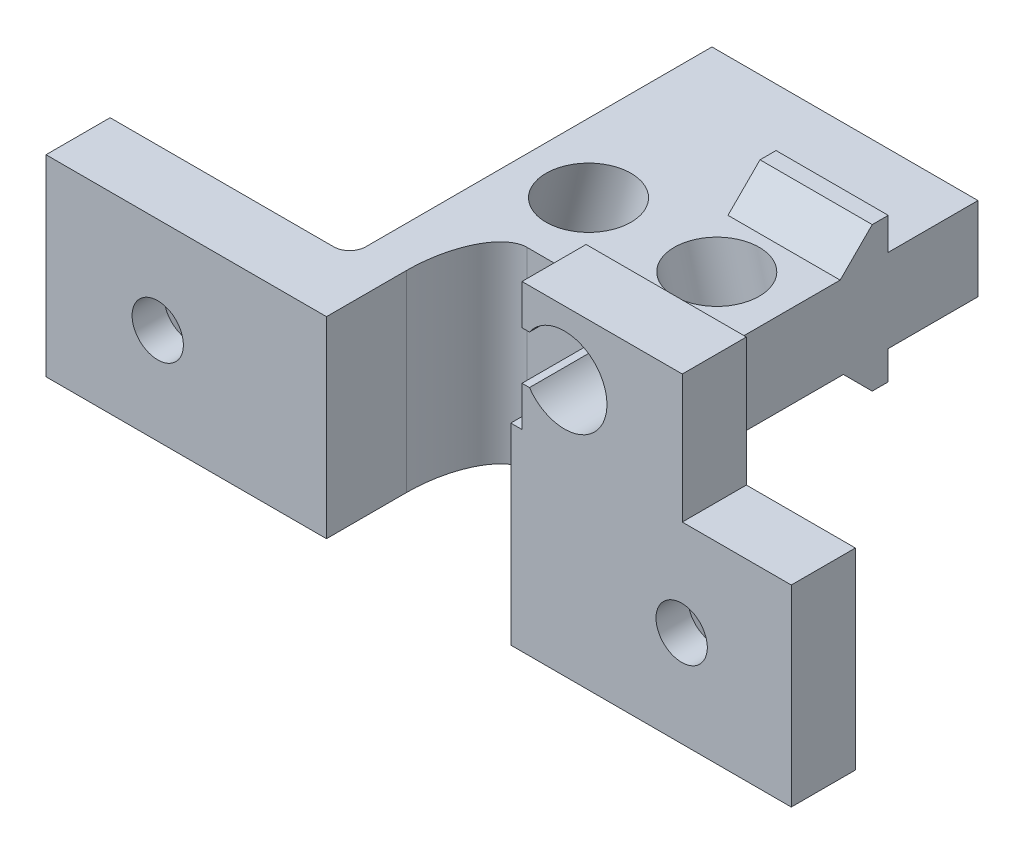
SolidWorks part; units mm, degrees
ref_plane "Front Plane" through (0, 0, 0) normal (0, 0, 1) x (1, 0, 0)
ref_plane "Top Plane" through (0, 0, 0) normal (0, 1, 0) x (1, 0, 0)
ref_plane "Right Plane" through (0, 0, 0) normal (1, 0, 0) x (0, 0, -1)
sketch "Sketch1" plane through (0, 0, 0) normal (0, 1, 0) x (1, 0, 0)
  line L0 (-3.25, -5) -> (-23.25, -5)
  line L1 (-3.25, -5) -> (3.25, -5) construction
  line L2 (-3.25, -5) -> (-3.25, 5) construction
  line L3 (-3.25, 5) -> (3.25, 5)
  line L4 (3.25, -5) -> (3.25, 5) construction
  line L5 (-3.25, -5) -> (3.25, 5) construction
  line L6 (-3.25, 5) -> (3.25, -5) construction
  line L7 (-23.25, -5) -> (-23.25, -1)
  line L8 (-23.25, -1) -> (-9.3, -1)
  line L9 (3.25, -5) -> (23.25, -5)
  line L10 (23.25, -5) -> (23.25, -3)
  line L12 (-8.3, 0) -> (-8.3, 6.6)
  line L13 (-8.3, 6.6) -> (8.3, 6.6)
  line L14 (8.3, 0) -> (8.3, 6.6)
  line L15 (-5.7498, 0) -> (-5.7498, -5)
  line L16 (5.7487, 0) -> (5.7487, -5)
  line L17 (23.25, -3) -> (23.25, -1)
  line L18 (23.25, -1) -> (9.3, -1)
  arc A0 (-9.3, -1) -> (-8.3, 0) centre (-9.3, 0) ccw
  arc A1 (9.3, -1) -> (8.3, 0) centre (9.3, 0) cw
  ellipse E0 centre (-3.25, 0) end of major axis (-3.25, 5) minor radius 2.4998 (-3.25, 5) -> (-3.25, -5) ccw
  ellipse E1 centre (3.25, 0) end of major axis (3.25, 5) minor radius 2.4987 (3.25, -5) -> (3.25, 5) ccw
  point P0 (0, 0)
  dimension "D6" = 1
  dimension "D7" = 4
  dimension "D12" = 1
  dimension "D1" = 6.5
  dimension "D2" = 10
  dimension "D3" = 20
  dimension "D4" = 4
  dimension "D5" = 20
  dimension "D8" = 16.6
  dimension "D9" = 1.6
  dimension "D10" = 5.05
  dimension "D11" = 5.05
extrude "Boss-Extrude1" add sketch "Sketch1" along normal blind 12 contours L8 L7 L0 E0 L3 E1 L9 L10 region at (-14.4999, 0, 4.5207)
sketch "Sketch2" plane through (0, 0, 1) normal (0, 0, -1) x (-1, 0, 0)
  line L0 (-23.3943, 12) -> (-9.4265, 0) construction
  line L1 (-23.25, 0) -> (-9.2822, 12) construction
  line L2 (23.25, 12) -> (9.3079, 0) construction
  line L3 (23.25, 0) -> (9.3, 0) construction
  line L4 (23.25, 0) -> (9.2822, 12) construction
  line L5 (-16.4104, 6) -> (-16.4104, -2.9743) construction
  line L6 (-16.4104, -0.7517) -> (-16.4104, 3) construction
  line L10 (16.2789, 6) -> (16.2789, -2.9743) construction
  line L11 (20.1472, 6) -> (18.2131, 9.35)
  line L12 (-12.5422, 6) -> (-14.4763, 9.35)
  line L13 (-14.4763, 9.35) -> (-18.3445, 9.35)
  line L14 (-18.3445, 9.35) -> (-20.2787, 6)
  line L15 (-20.2787, 6) -> (-18.3445, 2.65)
  line L16 (18.2131, 9.35) -> (14.3448, 9.35)
  line L17 (14.3448, 9.35) -> (12.4107, 6)
  line L18 (-18.3445, 2.65) -> (-14.4763, 2.65)
  line L19 (-14.4763, 2.65) -> (-12.5422, 6)
  line L20 (12.4107, 6) -> (14.3448, 2.65)
  line L21 (14.3448, 2.65) -> (18.2131, 2.65)
  line L22 (18.2131, 2.65) -> (20.1472, 6)
  circle A0 centre (-16.4104, 6) radius 3.35 construction
  circle A1 centre (16.2789, 6) radius 3.35 construction
  point P32 (11.4039, 0.6926)
  dimension "D1" = 6.7
  dimension "D2" = 6.7
extrude "Cut-Extrude1" cut sketch "Sketch2" against normal blind 2
sketch "Sketch3" plane through (0, 12, 0) normal (0, 1, 0) x (1, 0, 0)
  line L0 (-3.25, 5) -> (-3.25, 12.9854) construction
  line L1 (3.25, 5) -> (3.25, 12.9854) construction
  line L2 (-8.3, 6.6) -> (8.3, 6.6)
  line L3 (-8.1382, 9.4853) -> (3.25, 9.4853) construction
  line L4 (-10.9928, 20.2416) -> (10.7178, 20.2416) construction
  line L5 (-8.3, 6.6) -> (-8.3, 21.6)
  line L6 (-8.3, 21.6) -> (8.3, 21.6)
  line L7 (8.3, 21.6) -> (8.3, 6.6)
  circle A1 centre (3.25, 9.4853) radius 2.5 construction
  circle A3 centre (0, 0) radius 13.8 construction
  circle A4 centre (-3.25, 9.4853) radius 2.85 construction
  circle A5 centre (3.25, 9.4853) radius 2.85 construction
  circle A7 centre (0, 0) radius 13 construction
  line M20 (8.3, 6.6) -> (-8.3, 6.6)
  dimension "D1" = 20.2416
  dimension "D2" = 15
  dimension "D3" = 27.6
  dimension "D4" = 5.7
  dimension "D5" = 5.7
  dimension "D9" = 26
extrude "Boss-Extrude2" add sketch "Sketch3" against normal blind 5.2 contours M20 region at (0, 12, -14.1)
sketch "Sketch4" [suppressed] plane through (0, 6.8, 0) normal (0, -1, 0) x (1, 0, 0)
  line L0 (-8.3, -6.6) -> (8.3, -6.6)
  line L1 (8.3, -6.6) -> (8.3, -11.9594)
  line L2 (-8.3, -6.6) -> (-8.3, -9.2406)
  ellipse E1 centre (0, -10.6) end of major axis (8.3, -12.6) minor radius 3.3362 (-8.3, -9.2406) -> (8.3, -11.9594) ccw
  point P0 (0, 0)
extrude "Boss-Extrude3" [suppressed] add sketch "Sketch4" along normal blind 5
chamfer "Chamfer1" [suppressed] distance 0.5 angle 45
sketch "Sketch5" plane through (0, 0, 1) normal (0, 0, -1) x (-1, 0, 0)
  line L0 (12.4107, 6) -> (20.1472, 6) construction
  line L1 (20.1472, 6) -> (18.2131, 9.35) construction
  line L2 (20.1472, 6) -> (18.2131, 9.35) construction
  line L3 (16.2789, 9.35) -> (16.2789, 2.65) construction
  line L4 (18.2131, 9.35) -> (14.3448, 9.35) construction
  line L5 (14.3448, 2.65) -> (18.2131, 2.65) construction
  line L6 (-16.4104, 9.35) -> (-16.4104, 2.65) construction
  line L7 (-14.4763, 9.35) -> (-18.3445, 9.35) construction
  line L8 (-18.3445, 2.65) -> (-14.4763, 2.65) construction
  line L9 (-20.2787, 6) -> (-12.5422, 6) construction
  circle A0 centre (-16.4104, 6) radius 1.6
  circle A1 centre (16.2789, 6) radius 1.6
  dimension "D1" = 3.2
  dimension "D2" = 3.2
extrude "Cut-Extrude2" cut sketch "Sketch5" against normal blind 5
sketch "Sketch6" plane through (0, 12, 0) normal (0, 1, 0) x (1, 0, 0)
  line L0 (5.7487, -5) -> (23.25, -5) construction
  line L1 (6.4487, -5) -> (16.4487, -5)
  line L2 (6.4487, -5) -> (6.4487, -1)
  line L3 (6.4487, -1) -> (16.4487, -1)
  line L4 (16.4487, -5) -> (16.4487, -1)
  line L6 (5.7487, 0) -> (5.7487, -5) construction
  dimension "D1" = 4
  dimension "D2" = 0.7
  dimension "D3" = 10
extrude "Boss-Extrude4" add sketch "Sketch6" along normal blind 8
sketch "Sketch7" plane through (0, 0, 1) normal (0, 0, -1) x (-1, 0, 0)
  line L1 (-6.4487, 12) -> (-6.4487, 20) construction
  line L2 (-6.4487, 16) -> (-15.0595, 16) construction
  line L4 (-5.584, 17.5) -> (-7.9994, 17.5)
  line L5 (-5.584, 17.5) -> (-5.584, 14.5)
  line L6 (-5.584, 14.5) -> (-7.9994, 14.5)
  line L7 (-7.9994, 17.5) -> (-7.9994, 14.5)
  line L8 (-5.584, 17.5) -> (-7.9994, 14.5) construction
  line L9 (-5.584, 14.5) -> (-7.9994, 17.5) construction
  circle A0 centre (-9.0987, 16) radius 2.65
  point P6 (-6.7917, 16)
  line M11 (-6.4487, 12) -> (-6.4487, 20)
  dimension "D1" = 5.3
  dimension "D2" = 3
extrude "Cut-Extrude4" cut sketch "Sketch7" against normal blind 7 contours L4 A0 L6 L7 | A0 L4 L7 L6 | A0 L6 M11 | A0 L4 M11 region at (6.5859, 17.1319, 1) region at (7.292, 16, 1) region at (9.5241, 16, 1) region at (6.5859, 14.8681, 1)
sketch "Sketch8" plane through (0, 12, 0) normal (0, 1, 0) x (1, 0, 0)
  line L0 (8.3, 12.6) -> (-8.3, 12.6) construction
  line L1 (0, 12.6) -> (0, 3.5286) construction
  line L2 (-9.6265, 9.6) -> (9.6265, 9.6) construction
  line L4 (-3.25, 5) -> (3.25, 5) construction
  circle A0 centre (-4, 9.6) radius 2.65
  point P10 (0, 9.6)
  dimension "D2" = 5.3
  dimension "D3" = 7.6
  dimension "D1" = 3
  dimension "D4" = 4
sketch3d "3DSketch1"
  line L0 (0, 24, -5) -> (8.119, -6.3005, -5) construction
  line L1 (-3.25, 12, -5) -> (3.25, 12, -5) construction
  line L2 (3.25, 12, -5) -> (-3.25, 12, -5) construction
  line L3 (0, 12, -5) -> (0, -3.1746, -5) construction
  line L4 (0, 12, -5) -> (0, 24, -5) construction
  line L5 (0, 24, -5) -> (-8.2564, -6.8133, -5) construction
  point P7 (0, 12, -5)
  dimension "D1" = 12
  dimension "D2" = 15
  dimension "D3" = 15
extrude "Cut-Extrude5" cut sketch "Sketch8" along direction (-0.2588, -0.9659, 0) on the side against the normal blind 7
ref_plane "Plane1" through (8.119, -6.3005, -5) normal (0.2588, -0.9659, 0) x (-0.9659, -0.2588, 0)
sketch "Sketch10" plane through (0, 12, 0) normal (0, 1, 0) x (1, 0, 0)
  line L0 (-8.3, 12.6) -> (8.3, 12.6) construction
  line L1 (0, 12.6) -> (0, 2.6194) construction
  line L2 (-11.9688, 9.6) -> (11.9688, 9.6) construction
  line L3 (0, 5) -> (8.119, 5) construction
  circle A0 centre (4, 9.6) radius 2.65
  point P10 (0, 9.6)
  point P12 (0, 0)
  point P13 (0, 0)
  dimension "D3" = 5.3
  dimension "D1" = 3
  dimension "D2" = 4
  dimension "D4" = 7.6
extrude "Cut-Extrude6" cut sketch "Sketch10" along direction (0.2588, -0.9659, 0) on the side against the normal blind 7
sketch "Sketch11" plane through (0, 12, 0) normal (0, 1, 0) x (1, 0, 0)
  line L0 (-11.2946, 16) -> (11.8581, 16) construction
  line L1 (6.4487, -1) -> (6.4487, 20.4645) construction
  line L2 (8.3, 0) -> (8.3, 21.6) construction
  line L3 (1.3, 16) -> (8.3, 16)
  line L4 (1.3, 16) -> (1.3, 13)
  line L5 (1.3, 13) -> (8.3, 13)
  line L6 (8.3, 16) -> (8.3, 13)
  dimension "D1" = 16
  dimension "D2" = 7
  dimension "D3" = 3
extrude "Boss-Extrude6" add sketch "Sketch11" along normal blind 2 and the other way blind 7
chamfer "Chamfer2" distance 2 angle 45 2 edges at (4.8, 5, -13) (4.8, 14, -13)
